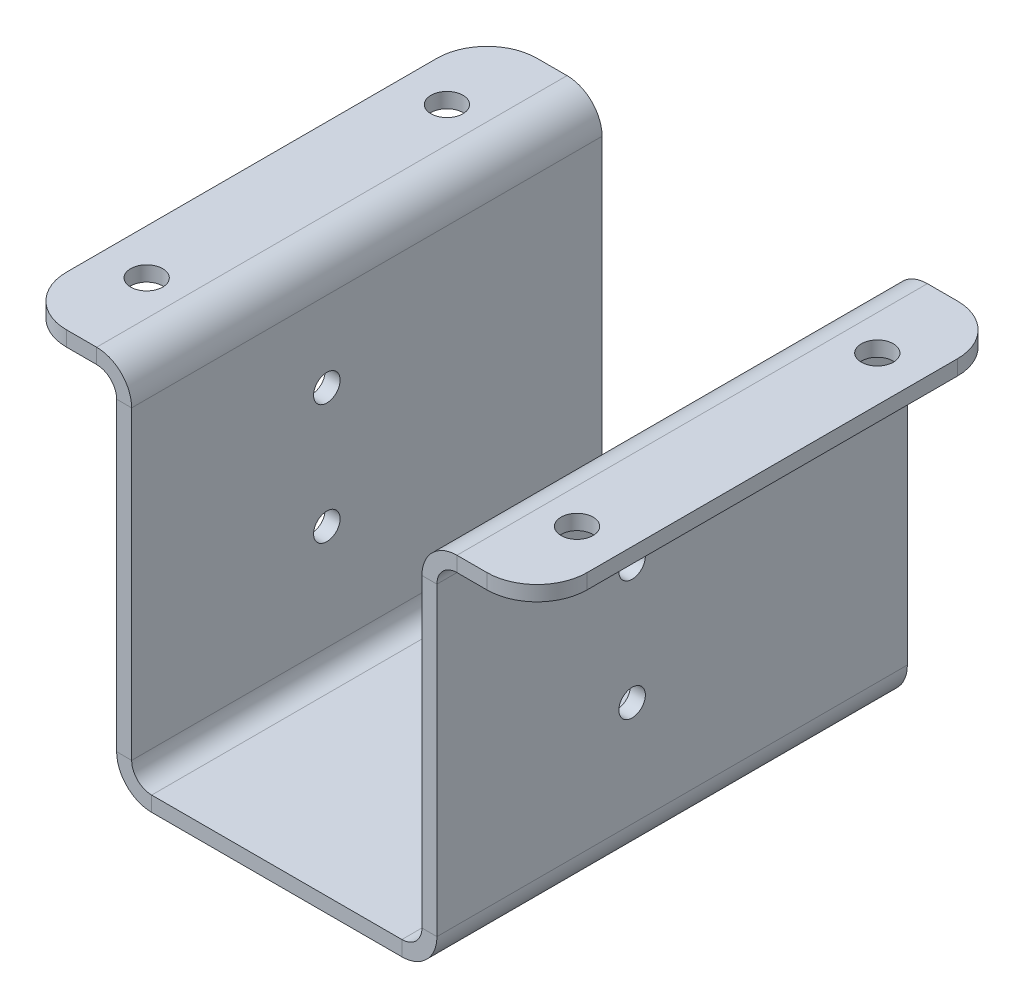
SolidWorks part; units mm, degrees
note: The reader was unsure of these and kept them because the rebuilt part matched: thickness of "Base-Flange1", "Edge-Flange1", "Edge-Flange2", "Sheet-Metal1", "Sheet-Metal2", "Sheet-Metal3", "Sheet-Metal4", "Sheet-Metal5", "Sheet-Metal6", "Sheet-Metal7"; flange length of "Edge-Flange1", "Edge-Flange2".
ref_plane "Front Plane" through (0, 0, 0) normal (0, 0, 1) x (1, 0, 0)
ref_plane "Top Plane" through (0, 0, 0) normal (0, 1, 0) x (1, 0, 0)
ref_plane "Right Plane" through (0, 0, 0) normal (1, 0, 0) x (0, 0, -1)
sketch "Sketch1" plane through (0, 0, 0) normal (0, 1, 0) x (1, 0, 0)
  line L1 (-14.5, -23.5) -> (14.5, -23.5)
  line L2 (-14.5, -23.5) -> (-14.5, 23.5)
  line L3 (-14.5, 23.5) -> (14.5, 23.5)
  line L4 (14.5, -23.5) -> (14.5, 23.5)
  line L5 (-14.5, -23.5) -> (14.5, 23.5) construction
  line L6 (-14.5, 23.5) -> (14.5, -23.5) construction
  point P0 (0, 0)
  dimension "D1" = 29
  dimension "D2" = 47
base flange "Base-Flange1" sketch "Sketch1" thickness 1.5 reverse thickness direction yes parameters "D1"=2
edge flange "Edge-Flange1" sketch "Sketch8" flange angle 90 flange length 36 flange position material outside bend radius 2 thickness 1.5 relief rectangular parameters "D6"=10
sketch "Sketch8" plane through (14.5, 1.5, 0) normal (-1, 0, 0) x (0, 0, 1)
  line L2 (-23.5, 0) -> (-23.5, 36)
  line L3 (-23.5, 36) -> (23.5, 36)
  line L4 (23.5, 36) -> (23.5, 0)
  line L5 (23.5, 0) -> (-23.5, 0) construction
  line L6 (23.5, 0) -> (-23.5, 0)
bend "EdgeBend1" bend radius 2 bend angle 90 parameters "D5"=1
mirror "Mirror1" about plane through (0, 0, 0) normal (1, 0, 0) of "Edge-Flange1"
bend "MirrorBend1" bend radius 2 bend angle 90 parameters "D5"=2
edge flange "Edge-Flange2" sketch "Sketch11" flange angle 90 flange length 10 flange position material inside bend radius 2 thickness 1.5 relief rectangular parameters "D6"=10
sketch "Sketch11" plane through (-16, 37.5, 0) normal (0, -1, 0) x (0, 0, 1)
  line L2 (-23.5, 0) -> (-23.5, 10)
  line L3 (-23.5, 10) -> (23.5, 10)
  line L4 (23.5, 10) -> (23.5, 0)
  line L5 (23.5, 0) -> (-23.5, 0) construction
  line L6 (23.5, 0) -> (-23.5, 0)
bend "EdgeBend2" bend radius 2 bend angle 90 parameters "D5"=3
mirror "Mirror2" about plane through (0, 0, 0) normal (1, 0, 0) of "Edge-Flange2"
bend "MirrorBend2" bend radius 2 bend angle 90 parameters "D5"=4
sketch "Sketch12" plane through (0, 37.5, 0) normal (0, 1, 0) x (1, 0, 0)
  line L0 (0, 0) -> (0, 50000) construction
  line L1 (0, 0) -> (50000, 0) construction
  circle A0 centre (21.5, 15) radius 1.6
  circle A1 centre (-21.5, 15) radius 1.6
  circle A2 centre (-21.5, -15) radius 1.6
  circle A3 centre (21.5, -15) radius 1.6
  dimension "D1" = 3.2
  dimension "D2" = 43
  dimension "D4" = 30
  dimension "D3" = 2
extrude "Cut-Extrude1" cut sketch "Sketch12" against normal blind 10
sketch "Sketch13" plane through (16, 0, 0) normal (1, 0, 0) x (0, 0, -1)
  line L0 (23.5, 0) -> (-23.5, 0) construction
  line L1 (-23.5, 3.5) -> (-23.5, 34) construction
  circle A0 centre (-4, 26) radius 1.325
  circle A1 centre (-4, 14) radius 1.325
  dimension "D3" = 2.65
  dimension "D1" = 26
  dimension "D2" = 12
  dimension "D4" = 19.5
extrude "Cut-Extrude2" cut sketch "Sketch13" against normal through all normal cut yes
fillet "Fillet1" radius 5 4 edges at (26, 36.75, -23.5) (26, 36.75, 23.5) (-26, 36.75, -23.5) (-26, 36.75, 23.5)
sketch "Bend-Lines1" [suppressed] plane through (0, 0, 0) normal (0, 1, 0) x (1, 0, 0)
sketch "Bounding-Box1" [suppressed] plane through (0, 0, 0) normal (0, 1, 0) x (1, 0, 0)
sheet metal parameters "Sheet-Metal1" thickness 1.5 parameters "D1"=2, "D7"=1
flat pattern "Flat-Pattern1" [suppressed]
sketch "Bend-Lines2" plane through (0, 0, 0) normal (0, 1, 0) x (1, 0, 0)
sketch3d "Bounding-Box2" [suppressed]
  line L0 (-14.5, -23.5, 0) -> (-14.5, 23.5, 0) construction
  line L1 (14.5, -23.5, 0) -> (14.5, 23.5, 0) construction
  line L2 (-14.5, -23.5, 0) -> (14.5, -23.5, 0) construction
  line L3 (-14.5, 23.5, 0) -> (14.5, 23.5, 0) construction
sheet metal parameters "Sheet-Metal2" thickness 1.5 parameters "D1"=2, "D7"=1
flat pattern "Flat-Pattern1"
sketch "Bend-Lines2" plane through (0, 0, 0) normal (0, -1, 0) x (-1, 0, 0)
  line L0 (-14.4164, 23.5) -> (-14.4164, -23.5) construction
  line L1 (-14.4164, 23.5) -> (-14.4164, -23.5) construction
sketch3d "Bounding-Box2" [suppressed]
  line L0 (-50.3327, 23.5, 0) -> (14.5, 23.5, 0) construction
  line L1 (-50.3327, -23.5, 0) -> (14.5, -23.5, 0) construction
  line L2 (-50.3327, 23.5, 0) -> (-50.3327, -23.5, 0) construction
  line L3 (14.5, 23.5, 0) -> (14.5, -23.5, 0) construction
bend of the flat pattern "Flatten-<EdgeBend1>1"
sheet metal parameters "Sheet-Metal3" thickness 1.5 parameters "D1"=2, "D7"=1
flat pattern "Flat-Pattern1"
sketch "Bend-Lines2" plane through (0, 0, 0) normal (0, -1, 0) x (-1, 0, 0)
  line L0 (-14.4164, 23.5) -> (-14.4164, -23.5) construction
  line L1 (-14.4164, 23.5) -> (-14.4164, -23.5) construction
  line L2 (14.4164, -23.5) -> (14.4164, 23.5) construction
  line L3 (14.4164, -23.5) -> (14.4164, 23.5) construction
sketch3d "Bounding-Box2" [suppressed]
  line L0 (-50.3327, 23.5, 0) -> (50.3327, 23.5, 0) construction
  line L1 (-50.3327, -23.5, 0) -> (50.3327, -23.5, 0) construction
  line L2 (-50.3327, 23.5, 0) -> (-50.3327, -23.5, 0) construction
  line L3 (50.3327, 23.5, 0) -> (50.3327, -23.5, 0) construction
bend of the flat pattern "Flatten-<EdgeBend1>1"
bend of the flat pattern "Flatten-<MirrorBend1>1"
sheet metal parameters "Sheet-Metal4" thickness 1.5 parameters "D1"=2, "D7"=1
flat pattern "Flat-Pattern1"
sketch "Bend-Lines2" plane through (0, 0, 0) normal (0, -1, 0) x (-1, 0, 0)
  line L0 (-14.4164, 23.5) -> (-14.4164, -23.5) construction
  line L1 (-14.4164, 23.5) -> (-14.4164, -23.5) construction
  line L2 (14.4164, -23.5) -> (14.4164, 23.5) construction
  line L3 (14.4164, -23.5) -> (14.4164, 23.5) construction
  line L4 (49.2491, -23.5) -> (49.2491, 23.5) construction
  line L5 (49.2491, -23.5) -> (49.2491, 23.5) construction
sketch3d "Bounding-Box2" [suppressed]
  line L0 (-50.3327, 23.5, 0) -> (59.1655, 23.5, 0) construction
  line L1 (-50.3327, -23.5, 0) -> (59.1655, -23.5, 0) construction
  line L2 (-50.3327, 23.5, 0) -> (-50.3327, -23.5, 0) construction
  line L3 (59.1655, 23.5, 0) -> (59.1655, -23.5, 0) construction
bend of the flat pattern "Flatten-<EdgeBend1>1"
bend of the flat pattern "Flatten-<MirrorBend1>1"
bend of the flat pattern "Flatten-<EdgeBend2>1"
sheet metal parameters "Sheet-Metal5" thickness 1.5 parameters "D1"=2, "D7"=1
flat pattern "Flat-Pattern1"
sketch "Bend-Lines2" plane through (0, 0, 0) normal (0, -1, 0) x (-1, 0, 0)
  line L0 (-14.4164, 23.5) -> (-14.4164, -23.5) construction
  line L1 (-14.4164, 23.5) -> (-14.4164, -23.5) construction
  line L2 (14.4164, -23.5) -> (14.4164, 23.5) construction
  line L3 (14.4164, -23.5) -> (14.4164, 23.5) construction
  line L4 (49.2491, -23.5) -> (49.2491, 23.5) construction
  line L5 (49.2491, -23.5) -> (49.2491, 23.5) construction
  line L6 (-49.2491, 23.5) -> (-49.2491, -23.5) construction
  line L7 (-49.2491, 23.5) -> (-49.2491, -23.5) construction
sketch3d "Bounding-Box2" [suppressed]
  line L0 (-59.1655, 23.5, 0) -> (59.1655, 23.5, 0) construction
  line L1 (-59.1655, -23.5, 0) -> (59.1655, -23.5, 0) construction
  line L2 (-59.1655, 23.5, 0) -> (-59.1655, -23.5, 0) construction
  line L3 (59.1655, 23.5, 0) -> (59.1655, -23.5, 0) construction
bend of the flat pattern "Flatten-<EdgeBend1>1"
bend of the flat pattern "Flatten-<MirrorBend1>1"
bend of the flat pattern "Flatten-<EdgeBend2>1"
bend of the flat pattern "Flatten-<MirrorBend2>1"
sheet metal parameters "Sheet-Metal6" thickness 1.5 parameters "D1"=2, "D7"=1
flat pattern "Flat-Pattern1"
sketch "Bend-Lines2" plane through (0, 0, 0) normal (0, -1, 0) x (-1, 0, 0)
  line L0 (-14.4164, 23.5) -> (-14.4164, -23.5) construction
  line L1 (-14.4164, 23.5) -> (-14.4164, -23.5) construction
  line L2 (14.4164, -23.5) -> (14.4164, 23.5) construction
  line L3 (14.4164, -23.5) -> (14.4164, 23.5) construction
  line L4 (49.2491, -23.5) -> (49.2491, 23.5) construction
  line L5 (49.2491, -23.5) -> (49.2491, 23.5) construction
  line L6 (-49.2491, 23.5) -> (-49.2491, -23.5) construction
  line L7 (-49.2491, 23.5) -> (-49.2491, -23.5) construction
sketch3d "Bounding-Box2" [suppressed]
  line L0 (-59.1655, 23.5, 0) -> (59.1655, 23.5, 0) construction
  line L1 (-59.1655, -23.5, 0) -> (59.1655, -23.5, 0) construction
  line L2 (-59.1655, 23.5, 0) -> (-59.1655, -23.5, 0) construction
  line L3 (59.1655, 23.5, 0) -> (59.1655, -23.5, 0) construction
bend of the flat pattern "Flatten-<EdgeBend1>1"
bend of the flat pattern "Flatten-<MirrorBend1>1"
bend of the flat pattern "Flatten-<EdgeBend2>1"
bend of the flat pattern "Flatten-<MirrorBend2>1"
sheet metal parameters "Sheet-Metal7" thickness 1.5 parameters "D1"=2, "D7"=1
flat pattern "Flat-Pattern1"
sketch "Bend-Lines2" plane through (0, 0, 0) normal (0, -1, 0) x (-1, 0, 0)
  line L0 (-14.5892, 23.5) -> (-14.5892, -23.5) construction
  line L1 (-14.5892, 23.5) -> (-14.5892, -23.5) construction
  line L2 (14.5892, -23.5) -> (14.5892, 23.5) construction
  line L3 (14.5892, -23.5) -> (14.5892, 23.5) construction
  line L4 (49.2675, -23.5) -> (49.2675, 23.5) construction
  line L5 (49.2675, -23.5) -> (49.2675, 23.5) construction
  line L6 (-49.2675, 23.5) -> (-49.2675, -23.5) construction
  line L7 (-49.2675, 23.5) -> (-49.2675, -23.5) construction
sketch3d "Bounding-Box2" [suppressed]
  line L0 (59.3566, 23.5, 0) -> (-59.3566, 23.5, 0) construction
  line L1 (59.3566, -23.5, 0) -> (-59.3566, -23.5, 0) construction
  line L2 (59.3566, 23.5, 0) -> (59.3566, -23.5, 0) construction
  line L3 (-59.3566, 23.5, 0) -> (-59.3566, -23.5, 0) construction
bend of the flat pattern "Flatten-<EdgeBend1>1"
bend of the flat pattern "Flatten-<MirrorBend1>1"
bend of the flat pattern "Flatten-<EdgeBend2>1"
bend of the flat pattern "Flatten-<MirrorBend2>1"
